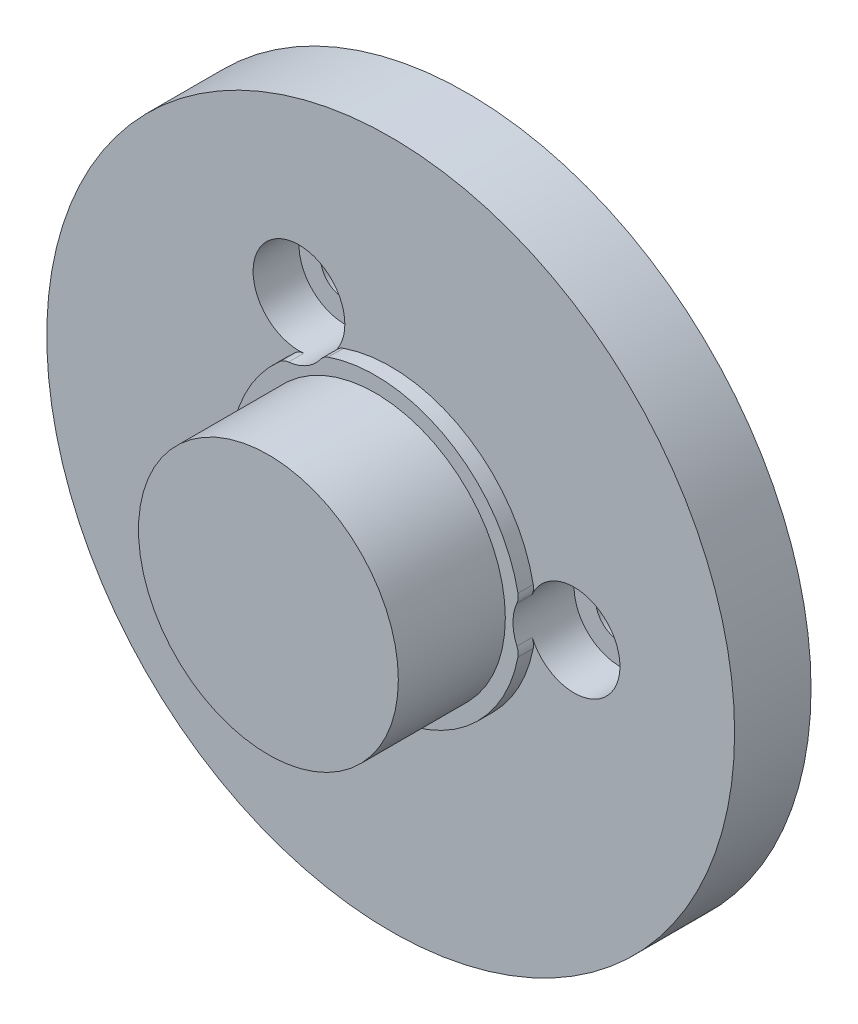
SolidWorks part; units mm, degrees
material "ABS"
ref_plane "Front Plane" through (0, 0, 0) normal (0, 0, 1) x (1, 0, 0)
ref_plane "Top Plane" through (0, 0, 0) normal (0, 1, 0) x (1, 0, 0)
ref_plane "Right Plane" through (0, 0, 0) normal (1, 0, 0) x (0, 0, -1)
sketch "Sketch1" plane through (0, 0, 31) normal (0, 0, 1) x (1, 0, 0)
  circle A0 centre (0, 0) radius 22.5
  circle A1 centre (-6, 10.3923) radius 1.6
  circle A2 centre (-6, -10.3923) radius 1.6
  circle A3 centre (12, 0) radius 1.6
  dimension "D1" = 45
  dimension "D2" = 3.2
  dimension "D3" = 3.2
  dimension "D4" = 3.2
extrude "Boss-Extrude1" add sketch "Sketch1" along normal blind 5
sketch "Sketch2" plane through (0, 0, 36) normal (0, 0, 1) x (1, 0, 0)
  circle A0 centre (-6, 10.3923) radius 3
  circle A1 centre (12, 0) radius 3
  circle A2 centre (-6, -10.3923) radius 3
  dimension "D1" = 6
  dimension "D2" = 6
  dimension "D3" = 6
extrude "Cut-Extrude1" cut sketch "Sketch2" against normal blind 3
sketch "Sketch3" plane through (0, 0, 36) normal (0, 0, 1) x (1, 0, 0)
  circle A0 centre (0, 0) radius 9.5
  circle M2 centre (-6, 10.3923) radius 3
  circle M3 centre (12, 0) radius 3
  circle M4 centre (-6, -10.3923) radius 3
  dimension "D1" = 19
extrude "Boss-Extrude2" add sketch "Sketch3" along normal blind 1 contours A0 M3 M2 M4 region at (0, 0, 36)
sketch "Sketch4" plane through (0, 0, 37) normal (0, 0, 1) x (1, 0, 0)
  circle A0 centre (0, 0) radius 8.5
  dimension "D1" = 17
extrude "Boss-Extrude3" add sketch "Sketch4" along normal blind 7 contours A0 region at (0, 0, 37)
fillet "Fillet1" radius 1 6 edges at (9.3854, 1.471, 36.5) (-5.9667, 7.3925, 36.5) (-3.4188, -8.8635, 36.5) (-3.4188, 8.8635, 36.5) (-5.9667, -7.3925, 36.5) (9.3854, -1.471, 36.5)
equation "\"thighLength\"=185"
equation "\"legLength\"=200"
equation "\"m3Thru\"=3.2"
equation "\"m4Thru\"=4.3"
equation "\"m3Insert\"=4.2"
equation "\"m4Insert\"=5.3"
equation "\"shoulder5mm\"=5.1"
equation "\"6706out\"=37.125"
equation "\"6706in\"=30"
equation "\"6904out\"=30.125"
equation "\"6904in\"=17"
equation "\"D2@Sketch1\"=\"m3Thru\""
equation "\"D3@Sketch1\"=\"m3Thru\""
equation "\"D4@Sketch1\"=\"m3Thru\""
